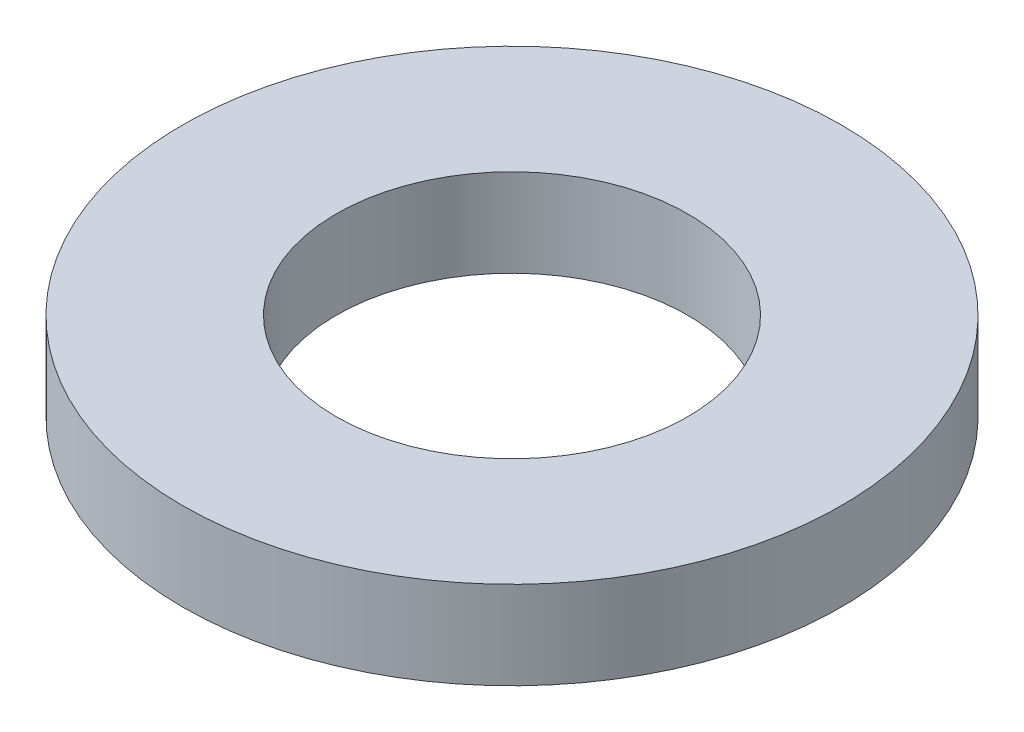
SolidWorks part; units mm, degrees
ref_plane "Front Plane" through (0, 0, 0) normal (0, 0, 1) x (1, 0, 0)
ref_plane "Top Plane" through (0, 0, 0) normal (0, 1, 0) x (1, 0, 0)
ref_plane "Right Plane" through (0, 0, 0) normal (1, 0, 0) x (0, 0, -1)
sketch "Sketch1" plane through (0, 0, 0) normal (0, 1, 0) x (1, 0, 0)
  circle A0 centre (0, 0) radius 75
  dimension "FLANGE_OD" = 150
extrude "Boss-Extrude1" add sketch "Sketch1" along normal blind 20
sketch "Sketch2" plane through (0, 0, 0) normal (0, 1, 0) x (1, 0, 0)
  circle A0 centre (0, 0) radius 40
  dimension "BORE_D" = 80
extrude "Cut-Extrude1" cut sketch "Sketch2" along normal through all
sketch "Sketch3" plane through (0, 20, 0) normal (0, 1, 0) x (1, 0, 0)
  circle A0 centre (0, 0) radius 23.6133 construction
  circle A1 centre (-23.6133, 0) radius 5.1431
  dimension "BOLT_D" = 10.2863
  dimension "BOLT_PCD" = 47.2266
extrude "Cut-Extrude2" cut sketch "Sketch3" against normal blind 13.7299 rebuild error yes
pattern_circular "CirPattern1" count 6 over 360 rebuild error yes
